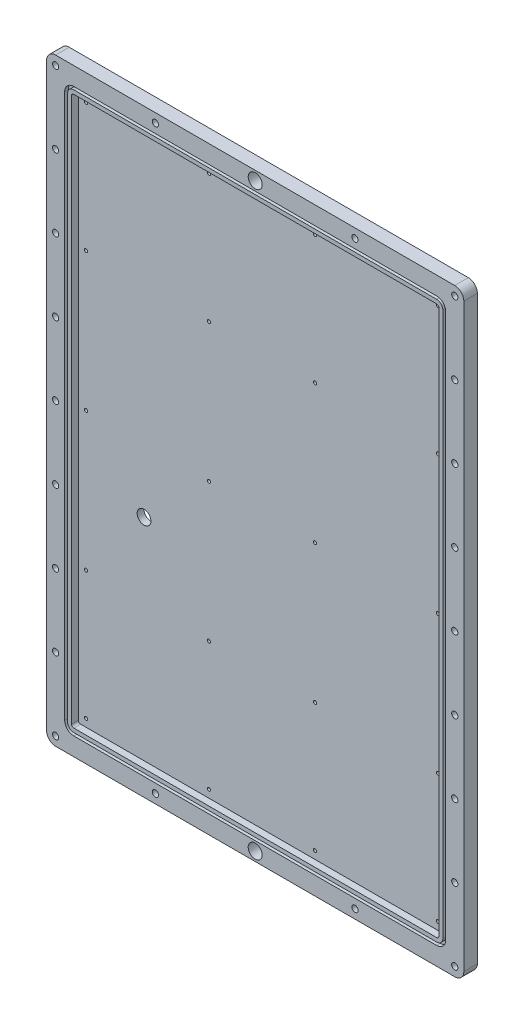
SolidWorks part; units mm, degrees
ref_plane "Front Plane" through (0, 0, 0) normal (0, 0, 1) x (1, 0, 0)
ref_plane "Top Plane" through (0, 0, 0) normal (0, 1, 0) x (1, 0, 0)
ref_plane "Right Plane" through (0, 0, 0) normal (1, 0, 0) x (0, 0, -1)
sketch "Sketch1" plane through (0, 0, 0) normal (0, 0, 1) x (1, 0, 0)
  line L1 (0, 0) -> (292.0492, 0)
  line L2 (0, 0) -> (0, 419.0492)
  line L3 (0, 419.0492) -> (292.0492, 419.0492)
  line L4 (292.0492, 0) -> (292.0492, 419.0492)
  dimension "D1" = 419.0492
  dimension "D2" = 292.0492
extrude "Boss-Extrude1" add sketch "Sketch1" along normal blind 9.525
sketch "Sketch4" plane through (0, 0, 9.525) normal (0, 0, 1) x (1, 0, 0)
  line L0 (91.477, 6.3246) -> (91.477, 0) construction
  line L1 (0, 0) -> (292.0492, 0) construction
  line L2 (6.3246, 94.9672) -> (0, 94.9672) construction
  line L4 (6.3246, 412.7246) -> (285.7246, 412.7246) construction
  line L5 (6.3246, 412.7246) -> (6.3246, 6.3246) construction
  line L6 (6.3246, 6.3246) -> (285.7246, 6.3246) construction
  line L7 (285.7246, 412.7246) -> (285.7246, 6.3246) construction
  line L11 (0, 419.0492) -> (0, 0) construction
  line L12 (285.7246, 110.613) -> (292.0492, 110.613) construction
  line L13 (292.0492, 0) -> (292.0492, 419.0492) construction
  line L14 (125.5626, 412.7246) -> (125.5626, 419.0492) construction
  line L15 (292.0492, 419.0492) -> (0, 419.0492) construction
  circle A0 centre (6.3246, 6.3246) radius 2.1844
  circle A1 centre (6.3246, 412.7246) radius 2.1844
  circle A2 centre (285.7246, 412.7246) radius 2.1844
  circle A3 centre (285.7246, 6.3246) radius 2.1844
  dimension "D5" = 4.3688
  dimension "D1" = 279.4
  dimension "D2" = 406.4
extrude "Cut-Extrude1" cut sketch "Sketch4" against normal through all
sketch "Sketch5" plane through (0, 0, 9.525) normal (0, 0, 1) x (1, 0, 0)
  line L0 (0, 209.5246) -> (12.6746, 209.5246) construction
  line L1 (19.0246, 406.3746) -> (273.0246, 406.3746)
  line L2 (12.6746, 400.0246) -> (12.6746, 19.0246)
  line L3 (19.0246, 12.6746) -> (273.0246, 12.6746)
  line L4 (279.3746, 400.0246) -> (279.3746, 19.0246)
  line L5 (0, 419.0492) -> (0, 0) construction
  line L6 (279.3746, 209.5246) -> (292.0492, 209.5246) construction
  line L8 (19.0246, 14.7066) -> (273.0246, 14.7066)
  line L9 (14.7066, 400.0246) -> (14.7066, 19.0246)
  line L10 (19.0246, 404.3426) -> (273.0246, 404.3426)
  line L11 (277.3426, 400.0246) -> (277.3426, 19.0246)
  line L12 (292.0492, 0) -> (292.0492, 419.0492) construction
  line L13 (146.0246, 12.6746) -> (146.0246, 0) construction
  line L14 (0, 0) -> (292.0492, 0) construction
  line L15 (146.0246, 406.3746) -> (146.0246, 419.0492) construction
  line L16 (292.0492, 419.0492) -> (0, 419.0492) construction
  arc A0 (273.0246, 12.6746) -> (279.3746, 19.0246) centre (273.0246, 19.0246) ccw
  arc A1 (12.6746, 19.0246) -> (19.0246, 12.6746) centre (19.0246, 19.0246) ccw
  arc A2 (273.0246, 406.3746) -> (279.3746, 400.0246) centre (273.0246, 400.0246) cw
  arc A3 (19.0246, 406.3746) -> (12.6746, 400.0246) centre (19.0246, 400.0246) ccw
  arc A4 (14.7066, 19.0246) -> (19.0246, 14.7066) centre (19.0246, 19.0246) ccw
  arc A5 (19.0246, 404.3426) -> (14.7066, 400.0246) centre (19.0246, 400.0246) ccw
  arc A6 (273.0246, 404.3426) -> (277.3426, 400.0246) centre (273.0246, 400.0246) cw
  arc A7 (273.0246, 14.7066) -> (277.3426, 19.0246) centre (273.0246, 19.0246) ccw
  dimension "D5" = 6.35
  dimension "D1" = 266.7
  dimension "D2" = 393.7
  dimension "D6" = 2.032
  dimension "D7" = 2.032
extrude "Cut-Extrude2" cut sketch "Sketch5" against normal blind 2.54 contours L1 A3 L2 A1 L3 A0 L4 A2 A7 L8 A4 L9 A5 L10 A6 L11 region at (146.0246, 405.8991, 9.525)
pattern_linear "LPattern3" count 4 spacing 69.85 along (1, 0, 0) of face at (8.509, 412.7246, 0) of face at (8.509, 6.3246, 0)
pattern_linear "LPattern4" count 8 spacing 50.8 along (0, -1, 0) of face at (8.509, 412.7246, 0) of face at (287.909, 412.7246, 0)
sketch "Sketch6" plane through (0, 0, 9.525) normal (0, 0, 1) x (1, 0, 0)
  line L4 (274.6121, 19.0246) -> (274.6121, 400.0246)
  line L5 (274.6121, 19.0246) -> (274.6121, 400.0246)
  line L6 (273.0246, 401.6121) -> (19.0246, 401.6121)
  line L7 (273.0246, 401.6121) -> (19.0246, 401.6121)
  line L8 (17.4371, 400.0246) -> (17.4371, 19.0246)
  line L9 (17.4371, 400.0246) -> (17.4371, 19.0246)
  line L10 (19.0246, 17.4371) -> (273.0246, 17.4371)
  line L11 (19.0246, 17.4371) -> (273.0246, 17.4371)
  arc A4 (273.0246, 17.4371) -> (274.6121, 19.0246) centre (273.0246, 19.0246) ccw
  arc A5 (273.0246, 17.4371) -> (274.6121, 19.0246) centre (273.0246, 19.0246) ccw
  arc A6 (274.6121, 400.0246) -> (273.0246, 401.6121) centre (273.0246, 400.0246) ccw
  arc A7 (274.6121, 400.0246) -> (273.0246, 401.6121) centre (273.0246, 400.0246) ccw
  arc A8 (19.0246, 401.6121) -> (17.4371, 400.0246) centre (19.0246, 400.0246) ccw
  arc A9 (19.0246, 401.6121) -> (17.4371, 400.0246) centre (19.0246, 400.0246) ccw
  arc A10 (17.4371, 19.0246) -> (19.0246, 17.4371) centre (19.0246, 19.0246) ccw
  arc A11 (17.4371, 19.0246) -> (19.0246, 17.4371) centre (19.0246, 19.0246) ccw
  dimension "D1" = 2.7305
extrude "Cut-Extrude3" cut sketch "Sketch6" against normal blind 4.7625
sketch "Sketch7" plane through (0, 0, 4.7625) normal (0, 0, 1) x (1, 0, 0)
  line L0 (273.0246, 401.6121) -> (19.0246, 401.6121) construction
  line L1 (22.8346, 396.2146) -> (269.2146, 396.2146) construction
  line L2 (22.8346, 396.2146) -> (22.8346, 22.8346) construction
  line L3 (22.8346, 22.8346) -> (269.2146, 22.8346) construction
  line L4 (269.2146, 396.2146) -> (269.2146, 22.8346) construction
  line L5 (17.4371, 400.0246) -> (17.4371, 19.0246) construction
  line L6 (274.6121, 19.0246) -> (274.6121, 400.0246) construction
  line L7 (269.2146, 112.649) -> (22.8346, 112.649) construction
  line L8 (17.4371, 400.0246) -> (17.4371, 19.0246) construction
  line L9 (274.6121, 19.0246) -> (274.6121, 400.0246) construction
  line L10 (269.2146, 209.5246) -> (22.8346, 209.5246) construction
  line L11 (183.1594, 396.2146) -> (183.1594, 22.8346) construction
  line L12 (108.8898, 22.8346) -> (108.8898, 396.2146) construction
  line L13 (269.2146, 306.4002) -> (22.8346, 306.4002) construction
  line L16 (19.0246, 17.4371) -> (273.0246, 17.4371) construction
  circle A0 centre (22.8346, 396.2146) radius 1.1303
  circle A1 centre (269.2146, 396.2146) radius 1.1303
  circle A2 centre (22.8346, 22.8346) radius 1.1303
  circle A3 centre (108.8898, 22.8346) radius 1.1303
  circle A4 centre (108.8898, 396.2146) radius 1.1303
  circle A5 centre (183.1594, 396.2146) radius 1.1303
  circle A6 centre (183.1594, 22.8346) radius 1.1303
  circle A7 centre (269.2146, 22.8346) radius 1.1303
  circle A8 centre (269.2146, 112.649) radius 1.1303
  circle A9 centre (108.8898, 112.649) radius 1.1303
  circle A10 centre (183.1594, 112.649) radius 1.1303
  circle A11 centre (22.8346, 112.649) radius 1.1303
  circle A12 centre (269.2146, 209.5246) radius 1.1303
  circle A13 centre (108.8898, 209.5246) radius 1.1303
  circle A14 centre (183.1594, 209.5246) radius 1.1303
  circle A15 centre (22.8346, 209.5246) radius 1.1303
  circle A16 centre (269.2146, 306.4002) radius 1.1303
  circle A17 centre (108.8898, 306.4002) radius 1.1303
  circle A18 centre (183.1594, 306.4002) radius 1.1303
  circle A19 centre (22.8346, 306.4002) radius 1.1303
  dimension "D5" = 2.2606
  dimension "D11" = 96.8756
  dimension "D9" = 373.38
  dimension "D13" = 86.0552
  dimension "D14" = 86.0552
  dimension "D1" = 5.3975
  dimension "D2" = 5.3975
  dimension "D3" = 5.3975
  dimension "D4" = 5.3975
  dimension "D6" = 91.4527
  dimension "D7" = 91.4527
  dimension "D8" = 91.4527
  dimension "D10" = 96.8756
  dimension "D12" = 91.4527
extrude "Cut-Extrude4" cut sketch "Sketch7" against normal blind 3.175
sketch "Sketch8" plane through (0, 0, 9.525) normal (0, 0, 1) x (1, 0, 0)
  circle A0 centre (146.0246, 412.7246) radius 4.9022
  circle A1 centre (146.0246, 6.3246) radius 4.9022
  dimension "D1" = 9.8044
extrude "Cut-Extrude5" cut sketch "Sketch8" against normal through all
fillet "Fillet1" radius 6.35 4 edges at (292.0492, 0, 4.7625) (0, 0, 4.7625) (292.0492, 419.0492, 4.7625) (0, 419.0492, 4.7625)
chamfer "Chamfer1" distance 2.54 angle 41 22 edges at (78.359, 412.7246, 0) (218.059, 412.7246, 0) (287.909, 412.7246, 0) (287.909, 361.9246, 0) (287.909, 311.1246, 0) (287.909, 260.3246, 0) (287.909, 209.5246, 0) (287.909, 158.7246, 0) (287.909, 107.9246, 0) (287.909, 57.1246, 0) (287.909, 6.3246, 0) (218.059, 6.3246, 0) (78.359, 6.3246, 0) (8.509, 6.3246, 0) (8.509, 57.1246, 0) (8.509, 107.9246, 0) (8.509, 158.7246, 0) (8.509, 260.3246, 0) (8.509, 311.1246, 0) (8.509, 412.7246, 0) (8.509, 361.9246, 0) (8.509, 209.5246, 0) first distance on face at (78.359, 412.7246, 0) first distance on face at (218.059, 412.7246, 0) first distance on face at (287.909, 412.7246, 0) first distance on face at (287.909, 361.9246, 0) first distance on face at (287.909, 311.1246, 0) first distance on face at (287.909, 260.3246, 0) first distance on face at (287.909, 209.5246, 0) first distance on face at (287.909, 158.7246, 0) first distance on face at (287.909, 107.9246, 0) first distance on face at (287.909, 57.1246, 0) first distance on face at (287.909, 6.3246, 0) first distance on face at (218.059, 6.3246, 0) first distance on face at (78.359, 6.3246, 0) first distance on face at (8.509, 6.3246, 0) first distance on face at (8.509, 57.1246, 0) first distance on face at (8.509, 107.9246, 0) first distance on face at (8.509, 158.7246, 0) first distance on face at (8.509, 260.3246, 0) first distance on face at (8.509, 311.1246, 0) first distance on face at (8.509, 412.7246, 0) first distance on face at (8.509, 361.9246, 0) first distance on face at (8.509, 209.5246, 0)
sketch "Sketch9" plane through (0, 0, 0) normal (0, 0, -1) x (-1, 0, 0)
  line L0 (-292.0492, 6.35) -> (-292.0492, 412.6992) construction
  line L1 (-6.35, 0) -> (-285.6992, 0) construction
  circle A0 centre (-63.4492, 165.1) radius 4.826
  dimension "D3" = 9.652
  dimension "D1" = 228.6
  dimension "D2" = 165.1
extrude "Cut-Extrude6" cut sketch "Sketch9" against normal through all
